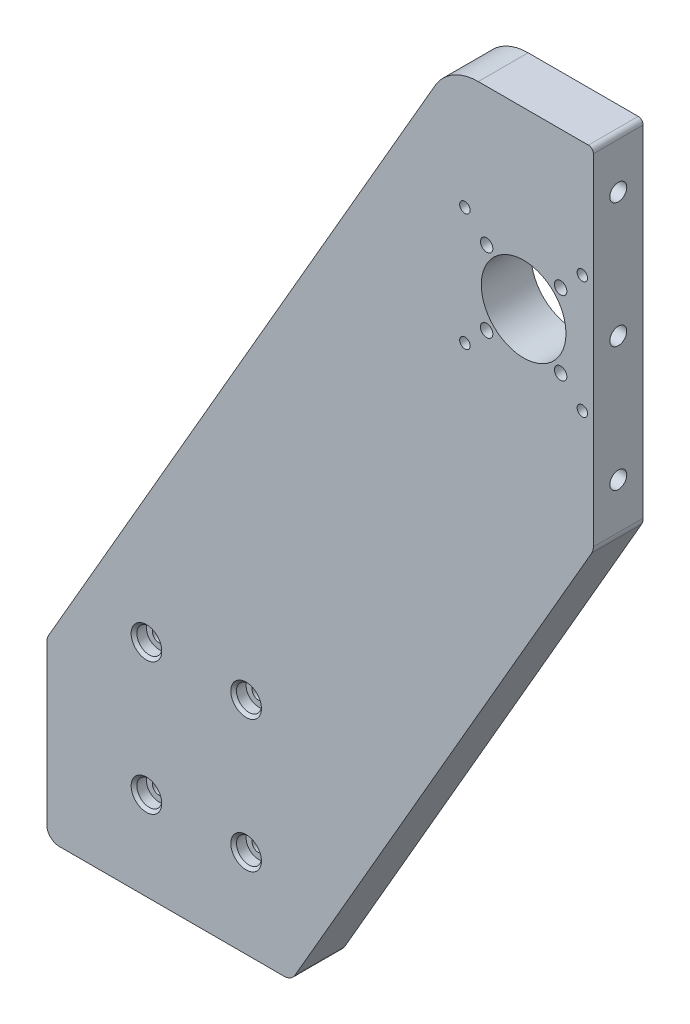
SolidWorks part; units mm, degrees
ref_plane "Piano frontale" through (0, 0, 0) normal (0, 0, 1) x (1, 0, 0)
ref_plane "Piano superiore" through (0, 0, 0) normal (0, 1, 0) x (1, 0, 0)
ref_plane "Piano destro" through (0, 0, 0) normal (1, 0, 0) x (0, 0, -1)
sketch "Schizzo1" plane through (0, 0, 0) normal (0, 0, 1) x (1, 0, 0)
  line L0 (5, 0) -> (95.2628, 0)
  line L1 (99.5929, 2.5) -> (218.7232, 208.8397)
  line L2 (219.3931, 211.3397) -> (219.3931, 348)
  line L3 (217.3931, 350) -> (173.2051, 350)
  line L4 (0, 68.6603) -> (0, 5)
  line L5 (155.8846, 340) -> (0.6699, 71.1603)
  line L6 (191.3931, 280) -> (191.3931, 350) construction
  line L9 (191.3931, 280) -> (176.5439, 294.8492) construction
  line L10 (191.3931, 280) -> (170.3931, 280) construction
  line L11 (191.3931, 280) -> (191.3931, 301) construction
  line L12 (50.1314, 0) -> (50.1314, 156.8301) construction
  circle A4 centre (191.3931, 280) radius 17
  circle A5 centre (191.3931, 280) radius 21 construction
  arc A6 (99.5929, 2.5) -> (95.2628, 0) centre (95.2628, 5) cw
  arc A7 (5, 0) -> (0, 5) centre (5, 5) cw
  arc A8 (0, 68.6603) -> (0.6699, 71.1603) centre (5, 68.6603) cw
  arc A9 (219.3931, 211.3397) -> (218.7232, 208.8397) centre (214.3931, 211.3397) cw
  arc A10 (219.3931, 348) -> (217.3931, 350) centre (217.3931, 348) ccw
  arc A11 (173.2051, 350) -> (155.8846, 340) centre (173.2051, 330) ccw
  circle A14 centre (206.2423, 294.8492) radius 2.5
  circle A15 centre (206.2423, 265.1508) radius 2.5
  circle A18 centre (176.5439, 265.1508) radius 2.5
  circle A19 centre (176.5439, 294.8492) radius 2.5
  point P27 (176.5439, 294.8492)
  point P28 (206.2423, 294.8492)
  point P29 (206.2423, 265.1508)
  point P30 (176.5439, 265.1508)
  point P31 (219.3931, 350)
  point P39 (0, 0)
  point P42 (0, 70)
  point P45 (219.3931, 210)
  point P48 (219.3931, 350)
  dimension "D6" = 70
  dimension "D9" = 34
  dimension "D11" = 45
  dimension "D14" = 5
  dimension "D15" = 5
  dimension "D17" = 42
  dimension "D12" = 2
  dimension "D1" = 120
  dimension "D2" = 120
  dimension "D3" = 70
  dimension "D4" = 350
  dimension "D5" = 140
  dimension "D10" = 28
extrude "Estrusione-Estrusione2" add sketch "Schizzo1" against normal blind 20
sketch "Sketch1" plane through (0, 0, 0) normal (0, -1, 0) x (1, 0, 0)
  line L0 (5, -10) -> (95.2628, -10) construction
  line L1 (5, -20) -> (5, 0) construction
  line L2 (95.2628, -20) -> (95.2628, 0) construction
  line L3 (50.1314, 0) -> (50.1314, -20) construction
  line L4 (5, 0) -> (95.2628, 0) construction
  line L5 (5, -20) -> (95.2628, -20) construction
  point P12 (50.1314, -10)
  point P13 (85.1314, -10)
  point P14 (15.1314, -10)
  dimension "D1" = 35
hole_wizard "M5 Tapped Hole1" positions "3DSketch1" profile "Sketch2" tap size "M5" standard "ISO"
sketch3d "3DSketch1"
  point P0 (50.1314, 0, -10)
  point P3 (85.1314, 0, -10)
  point P6 (15.1314, 0, -10)
sketch "Sketch2" plane through (50.1314, 0, -10) normal (1, 0, 0) x (0, 0, -1)
  line L0 (0, 0) -> (0, 18.6618)
  line L1 (0, 18.6618) -> (2.1, 17.4)
  line L2 (2.1, 17.4) -> (2.1, 0)
  line L5 (2.1, 0) -> (0, 0)
  line L10 (0, 18.6618) -> (-2.1, 17.4) construction
  line L11 (0, -6.35) -> (0, 107.95) construction
  dimension "Tap Drill Dia." = 4.2
  dimension "Tap Drill Depth" = 17.4
  dimension "Drill Angle" = 118
sketch "Sketch3" plane through (0, 0, 0) normal (0, 0, 1) x (1, 0, 0)
  line L0 (0, 68.6603) -> (0, 5) construction
  point P0 (40, 88.5)
  point P1 (80, 88.5)
  point P2 (80, 35.5)
  point P3 (40, 35.5)
  dimension "D1" = 40
  dimension "D2" = 53
  dimension "D3" = 40
hole_wizard "CBORE for M5 SHCS1" positions "3DSketch3" profile "Sketch5" counterbore size "M5" standard "ANSI Metric" end condition through all
sketch3d "3DSketch3"
  point P0 (80, 88.5, 0)
  point P3 (80, 35.5, 0)
  point P6 (40, 35.5, 0)
  point P9 (40, 88.5, 0)
sketch "Sketch5" plane through (80, 88.5, 0) normal (1, 0, 0) x (0, -1, 0)
  line L0 (0, 0) -> (0, 20)
  line L1 (0, 20) -> (2.65, 20)
  line L3 (2.65, 20) -> (2.65, 5)
  line L4 (5, 5) -> (2.65, 5)
  line L5 (5, 5) -> (5, 1.145)
  line L6 (5, 1.145) -> (6.145, 0)
  line L7 (6.145, 0) -> (0, 0)
  line L8 (-5, 1.145) -> (-6.145, 0) construction
  line L11 (0, -6.35) -> (0, 107.95) construction
  dimension "Thru Hole Dia." = 5.3
  dimension "Thru Hole Depth" = 20
  dimension "C'Bore Dia." = 10
  dimension "C'Bore Depth" = 5
  dimension "Near C'Sink Dia." = 12.29
  dimension "Near C'Sink Angle" = 90
sketch "Sketch7" plane through (219.3931, 0, 0) normal (1, 0, 0) x (0, 0, -1)
  line L0 (20, 279.6699) -> (0, 279.6699) construction
  line L1 (20, 211.3397) -> (20, 348) construction
  line L2 (0, 211.3397) -> (0, 348) construction
  point P0 (10, 329.6699)
  point P2 (10, 279.6699)
  point P4 (10, 229.6699)
  dimension "D1" = 50
  dimension "D2" = 50
hole_wizard "M8 Tapped Hole1" positions "3DSketch6" profile "Sketch12" tap size "M8" standard "ISO"
sketch3d "3DSketch6"
  point P0 (219.3931, 329.6699, -10)
  point P6 (219.3931, 279.6699, -10)
  point P12 (219.3931, 229.6699, -10)
sketch "Sketch12" plane through (219.3931, 329.6699, -10) normal (0, 1, 0) x (0, 0, -1)
  line L0 (0, 0) -> (0, 17.7929)
  line L1 (0, 17.7929) -> (3.4, 15.75)
  line L2 (3.4, 15.75) -> (3.4, 0)
  line L5 (3.4, 0) -> (0, 0)
  line L10 (0, 17.7929) -> (-3.4, 15.75) construction
  line L11 (0, -6.35) -> (0, 107.95) construction
  dimension "Tap Drill Dia." = 6.8
  dimension "Tap Drill Depth" = 15.75
  dimension "Drill Angle" = 118
sketch "Sketch24" plane through (0, 0, 0) normal (0, 0, 1) x (1, 0, 0)
  line L0 (191.3931, 280) -> (191.3931, 322.4149) construction
  line L1 (191.3931, 280) -> (226.3538, 280) construction
  point P3 (214.9631, 303.57)
  point P7 (167.8231, 303.57)
  point P8 (214.9631, 256.43)
  point P9 (167.8231, 256.43)
  dimension "D1" = 23.57
  dimension "D2" = 23.57
hole_wizard "M5 Tapped Hole2" positions "3DSketch9" profile "Sketch26" tap size "M5" standard "ISO" end condition through all
sketch3d "3DSketch9"
  point P0 (214.9631, 303.57, 0)
  point P3 (167.8231, 303.57, 0)
  point P6 (167.8231, 256.43, 0)
  point P9 (214.9631, 256.43, 0)
sketch "Sketch26" plane through (214.9631, 303.57, 0) normal (1, 0, 0) x (0, -1, 0)
  line L0 (0, 0) -> (0, 20)
  line L1 (0, 20) -> (2.1, 20)
  line L2 (2.1, 20) -> (2.1, 0)
  line L5 (2.1, 0) -> (0, 0)
  line L11 (0, -6.35) -> (0, 107.95) construction
  dimension "Thru Tap Drill Dia." = 4.2
  dimension "Thru Tap Drill Depth" = 20
cosmetic thread "Hole Thread1" parameters "D2"=5
cosmetic thread "Hole Thread2" parameters "D2"=5
cosmetic thread "Hole Thread3" parameters "D2"=5
cosmetic thread "Hole Thread4" parameters "D2"=5
